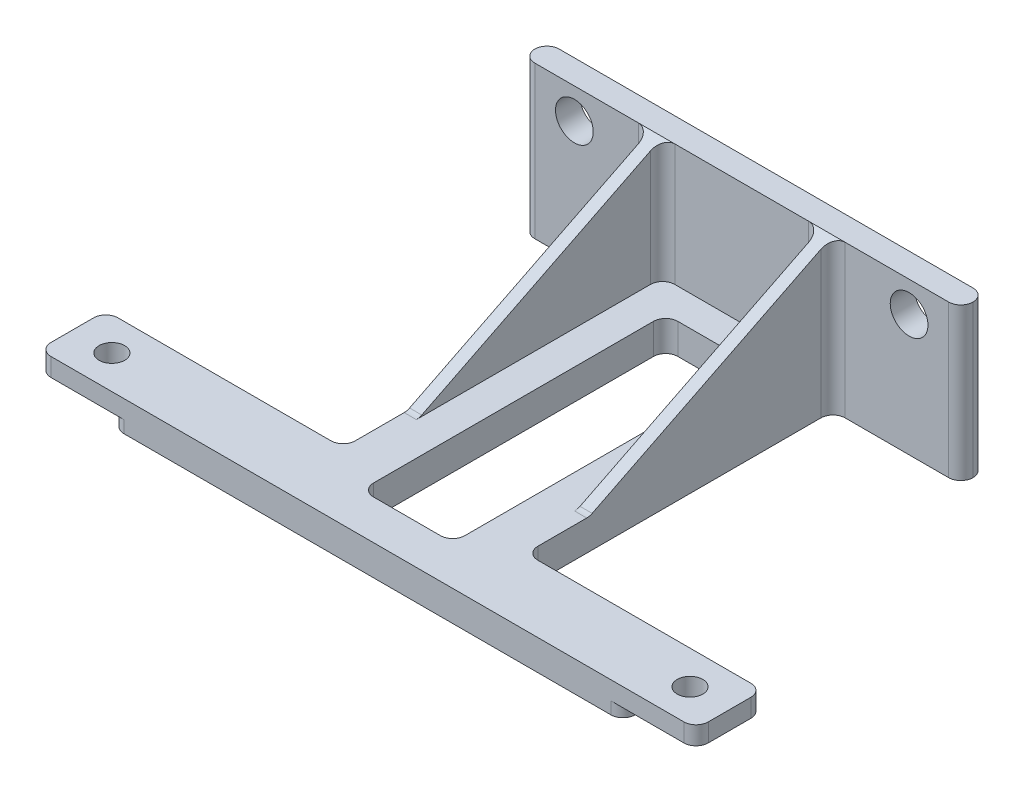
SolidWorks part; units mm, degrees
ref_plane "前视基准面" through (0, 0, 0) normal (0, 0, 1) x (1, 0, 0)
ref_plane "上视基准面" through (0, 0, 0) normal (0, 1, 0) x (1, 0, 0)
ref_plane "右视基准面" through (0, 0, 0) normal (1, 0, 0) x (0, 0, -1)
sketch "草图1" plane through (0, 0, 0) normal (0, 0, 1) x (1, 0, 0)
  line L0 (0, -341.5162) -> (0, 16734.2928) construction
  line L1 (-1000, 0) -> (49000, 0) construction
  line L2 (-36, -12.5) -> (36, -12.5)
  line L3 (-36, -12.5) -> (-36, 12.5)
  line L4 (-36, 12.5) -> (36, 12.5)
  line L5 (36, -12.5) -> (36, 12.5)
  line L6 (-36, -12.5) -> (36, 12.5) construction
  line L7 (-36, 12.5) -> (36, -12.5) construction
  circle A0 centre (-27.5, 7.5) radius 3.1
  circle A1 centre (27.5, 7.5) radius 3.1
  point P1 (0, 0)
  point P14 (-27.5, -4.8683)
  dimension "D2" = 6.2
  dimension "D3" = 27.5
  dimension "D5" = 20
  dimension "D1" = 25
  dimension "D4" = 72
extrude "凸台-拉伸1" add sketch "草图1" along normal blind 4
sketch "草图3" plane through (0, 0, 4) normal (0, 0, 1) x (1, 0, 0)
  line L0 (0, -1000) -> (0, 49000) construction
  line L1 (-36, -12.5) -> (36, -12.5) construction
  line L2 (-15, -7.5) -> (15, -7.5)
  line L3 (-15, -7.5) -> (-15, -12.5)
  line L4 (-15, -12.5) -> (15, -12.5)
  line L5 (15, -7.5) -> (15, -12.5)
  line L6 (-15, -7.5) -> (15, -12.5) construction
  line L7 (-15, -12.5) -> (15, -7.5) construction
  point P1 (0, -10)
  dimension "D1" = 5
  dimension "D2" = 30
extrude "凸台-拉伸2" add sketch "草图3" along normal blind 60 from surface starting at face at (-24.4, 7.5, 0)
sketch "草图5" plane through (0, -7.5, 0) normal (0, 1, 0) x (1, 0, 0)
  line L0 (-1007.641, -60) -> (48992.359, -60) construction
  line L2 (15, -60) -> (-15, -60) construction
  line L4 (0, -989.2683) -> (0, 48741.716) construction
  line L5 (-54, -65.5) -> (54, -65.5)
  line L6 (-54, -65.5) -> (-54, -54.5)
  line L7 (-54, -54.5) -> (54, -54.5)
  line L8 (54, -65.5) -> (54, -54.5)
  line L9 (-54, -65.5) -> (54, -54.5) construction
  line L10 (-54, -54.5) -> (54, -65.5) construction
  circle A0 centre (47.5, -60) radius 2.1
  circle A1 centre (-47.5, -60) radius 2.1
  point P7 (0, -60)
  dimension "D1" = 4.2
  dimension "D2" = 47.5
  dimension "D3" = 11
  dimension "D4" = 108
extrude "凸台-拉伸3" add sketch "草图5" against normal through all
sketch "草图6" plane through (0, -7.5, 0) normal (0, 1, 0) x (1, 0, 0)
  line L0 (-15, -54.5) -> (-54, -54.5) construction
  line L2 (0, -1000) -> (0, 49000) construction
  line L3 (-54, -65.5) -> (-42, -65.5)
  line L4 (-54, -65.5) -> (-54, -54.5)
  line L5 (-54, -54.5) -> (-42, -54.5)
  line L6 (-42, -65.5) -> (-42, -54.5)
  line L7 (54, -54.5) -> (42, -54.5)
  line L8 (42, -65.5) -> (42, -54.5)
  line L9 (54, -65.5) -> (42, -65.5)
  line L10 (54, -65.5) -> (54, -54.5)
  dimension "D1" = 12
extrude "切除-拉伸1" cut sketch "草图6" along normal blind 2 from surface starting at face at (0, -12.5, 30.4167)
sketch "草图7" plane through (0, -7.5, 0) normal (0, 1, 0) x (1, 0, 0)
  line L0 (0, -1000) -> (0, 49000) construction
  line L1 (36, -4) -> (-36, -4) construction
  line L2 (-7.5, -59) -> (7.5, -59)
  line L3 (-7.5, -59) -> (-7.5, -9)
  line L4 (-7.5, -9) -> (7.5, -9)
  line L5 (7.5, -59) -> (7.5, -9)
  line L6 (-7.5, -59) -> (7.5, -9) construction
  line L7 (-7.5, -9) -> (7.5, -59) construction
  point P1 (0, -34)
  dimension "D1" = 15
  dimension "D2" = 50
  dimension "D3" = 5
extrude "切除-拉伸2" cut sketch "草图7" against normal through all
sketch "草图8" plane through (-15, 0, 0) normal (-1, 0, 0) x (0, 0, 1)
  line L0 (4, -7.5) -> (44, -7.5)
  line L2 (44, -7.5) -> (4, 12.5)
  line L3 (4, 12.5) -> (4, -7.5)
  dimension "D1" = 40
extrude "凸台-拉伸4" add sketch "草图8" against normal blind 2
extrude "凸台-拉伸5" add sketch "草图8<2>" along normal blind 2 from surface starting at face at (15, -10, 29.25)
sketch "草图8<2>" plane through (-15, 0, 0) normal (-1, 0, 0) x (0, 0, 1) same geometry as "草图8"
fillet "圆角1" radius 2 24 edges at (15, 0, 4) (36, 0, 4) (36, 0, 0) (-36, 0, 0) (-36, 0, 4) (-15, -10, 54.5) (-54, -9, 54.5) (-54, -9, 65.5) (54, -9, 65.5) (54, -9, 54.5) (15, -10, 54.5) (-15, 0, 4) (-42, -11.5, 54.5) (42, -11.5, 54.5) (42, -11.5, 65.5) (-42, -11.5, 65.5) (-7.5, -10, 59) (-7.5, -10, 9) (7.5, -10, 59) (7.5, -10, 9) (14, -7.5, 44) (-14, -7.5, 44) (-13, 2.5, 4) (13, 2.5, 4)
